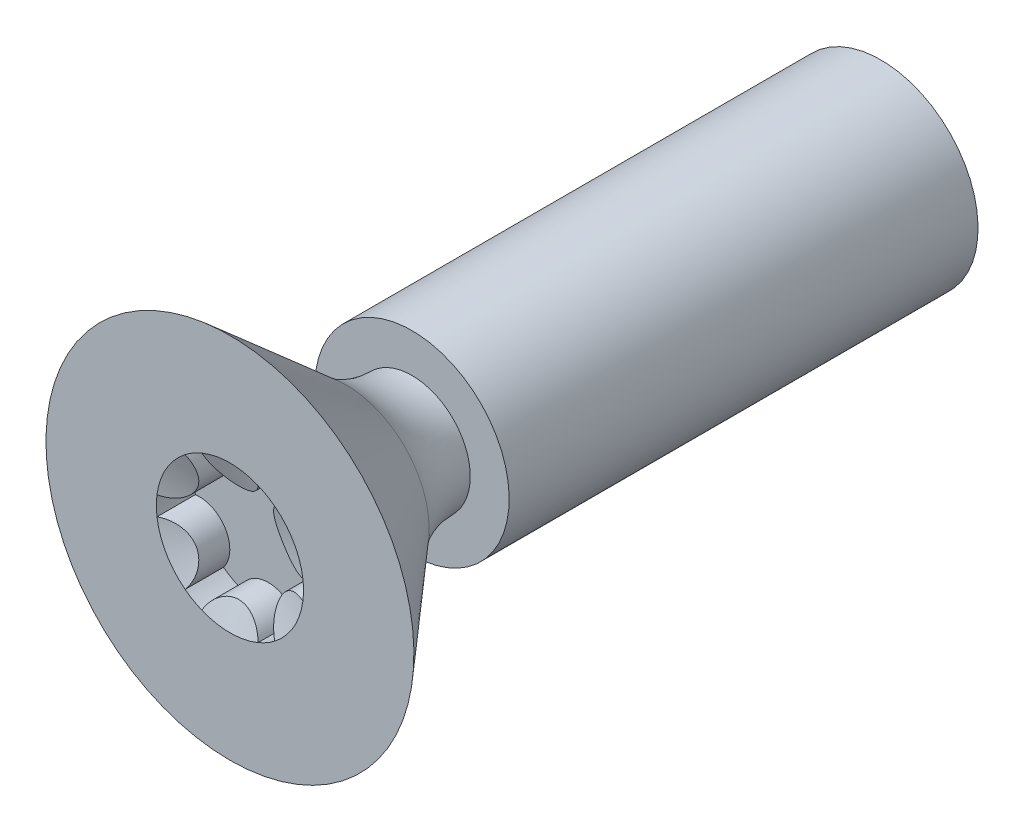
SolidWorks part; units mm, degrees
material "Plain Carbon Steel"
ref_plane "Front Plane" through (0, 0, 0) normal (0, 0, 1) x (1, 0, 0)
ref_plane "Top Plane" through (0, 0, 0) normal (0, 1, 0) x (1, 0, 0)
ref_plane "Right Plane" through (0, 0, 0) normal (1, 0, 0) x (0, 0, -1)
sketch "Sketch1" plane through (0, 0, 0) normal (1, 0, 0) x (0, 0, -1)
  line L0 (-4.7625, 0) -> (4.7625, 0) construction
  line L1 (4.7625, 0) -> (4.7625, 1.4224) construction
  line L2 (4.7625, 1.4224) -> (-3.0607, 1.4224) construction
  line L4 (-4.7625, 2.6924) -> (-4.7625, 0) construction
  line L5 (4.7625, -1.4224) -> (4.7625, 1.4224) construction
  line L6 (4.6831, 1.5599) -> (5.3181, 0.46) construction
  line L7 (5.3181, 0.46) -> (5.9531, 1.5599) construction
  line L8 (5.9531, 1.5599) -> (4.6831, 1.5599) construction
  line L9 (5.3181, 0.46) -> (5.3181, 0.5975) construction
  line L10 (5.3181, 1.5599) -> (5.3181, 1.4224) construction
  line L11 (5.8738, 1.4224) -> (4.7625, 1.4224) construction
  line L12 (5.3181, 1.4911) -> (5.9134, 1.4911) construction
  line L13 (5.3181, 1.4911) -> (4.7228, 1.4911) construction
  line L14 (5.2388, 0.5975) -> (5.3975, 0.5975) construction
  line L15 (-4.7625, 2.6924) -> (-3.0607, 0.7347) construction
  line L16 (2.8575, 1.4224) -> (2.8575, 0) construction
  line L17 (2.8575, 1.4224) -> (3.4925, 1.3104) construction
  line L18 (3.4925, 1.3104) -> (4.1275, 1.1985) construction
  line L19 (4.1275, 1.1985) -> (4.7625, 1.0865) construction
  line L20 (-4.7625, 0.7347) -> (-3.0607, 0.7347) construction
  line L21 (-3.0607, 1.4224) -> (-3.0607, 0.7347) construction
  line L22 (-3.1639, 0.8534) -> (2.8575, 0.8534) construction
  line L23 (-4.7625, 2.6924) -> (-2.647, 0.8534) construction
  line L24 (5.091, 0.8534) -> (5.5453, 0.8534) construction
  line L25 (-2.4257, 1.4224) -> (-2.9947, 0.8534) construction
  line L26 (-4.7625, 2.1336) -> (-2.3749, 0) construction
  line L27 (-4.7625, 0.3683) -> (-2.787, 0.3683) construction
  line L28 (-2.647, 0.8534) -> (-1.6652, 0) construction
  line L30 (-2.0989, 0) -> (-2.0989, 1.4224) construction
  line L31 (-1.1464, 0) -> (-1.1464, 1.4224) construction
  arc A1 (-3.2316, 0.9313) -> (-3.0607, 0.8534) centre (-3.0607, 1.0799) ccw construction
  arc A2 (-3.0607, 1.213) -> (-2.0989, 0.8534) centre (-2.0989, 2.3195) ccw construction
  point P0 (0.9525, 1.4224)
  point P4 (0, 0)
  point P10 (4.7625, 0)
  point P41 (-2.833, 1.0151)
  point P45 (-4.7625, 1.077)
  point P55 (-4.252, 0.7347)
  dimension "Length" = 9.525
  dimension "Screw OD" = 2.8448
  dimension "Head DIa" = 5.3848
  dimension "Pitch" = 1.27
  dimension "D2" = 0.1588
  dimension "D3" = 41
  dimension "D4" = 10
  dimension "D5" = 1.27
  dimension "Head Ht" = 1.7018
  dimension "D6" = 0.569
  dimension "D1" = 3.81
  dimension "D7" = 49
  dimension "D8" = 45
  dimension "D9" = 0.635
  dimension "D10" = 2.1539
  dimension "Recess Wd" = 0.7366
  dimension "Recess Dia" = 4.2672
  dimension "Recess Dp" = 2.3876
  dimension "D11" = 0.9525
  dimension "D12" = 0.5105
sketch "Sketch2" plane through (0, 0, 0) normal (0, 0, 1) x (1, 0, 0)
  line L0 (0, 0) -> (1.2318, -0.7112) construction
  line L1 (0, 0) -> (-1.2318, -0.7112) construction
  line L2 (0, 0.46) -> (0, 1.5599) construction
  line L5 (0, 2.6924) -> (0, 0) construction
  line L12 (0, 0) -> (0.5385, 0.9327) construction
  line L13 (0, 0) -> (-0.5385, 0.9327) construction
  line L14 (0, 0) -> (-0.4121, 0.995) construction
  line L15 (0, 0) -> (0.4121, 0.995) construction
  line L17 (0, -1.4224) -> (0, 1.4224) construction
  circle A7 centre (0, 0) radius 1.4224 construction
  circle A9 centre (0, 0) radius 1.077 construction
  arc A10 (-0.4121, 0.995) -> (0.4121, 0.995) centre (0, 1.1657) ccw construction
  arc A11 (-0.2886, 1.3437) -> (0.2886, 1.3437) centre (0, 0.8534) cw construction
  arc A12 (-1.308, -0.4219) -> (-1.0194, -0.9218) centre (-0.7391, -0.4267) ccw construction
  arc A13 (1.308, -0.4219) -> (1.0194, -0.9218) centre (0.7391, -0.4267) cw construction
  arc A14 (-1.308, -0.4219) -> (-0.2886, 1.3437) centre (0.7611, -0.4394) cw construction
  arc A15 (0.2886, 1.3437) -> (1.308, -0.4219) centre (-0.7611, -0.4394) cw construction
  arc A16 (1.0194, -0.9218) -> (-1.0194, -0.9218) centre (0, 0.8788) cw construction
  circle A17 centre (0, 0) radius 0.8534 construction
  point P0 (0, 2.6924)
  point P17 (1.2318, -0.7112)
  point P19 (-1.2318, -0.7112)
  point P21 (0, 0.8534)
  point P22 (1.2318, -0.7112)
  point P25 (0, -1.1904)
  point P26 (-1.2318, -0.7112)
  point P29 (0, 1.4224)
  point P66 (-0.7391, -0.4267)
  dimension "D1" = 0.569
  dimension "D2" = 120
  dimension "D3" = 120
  dimension "D6" = 7.5
  dimension "D7" = 7.5
  dimension "D8" = 30
  dimension "D9" = 30
  dimension "D4" = 0.0254
sketch "Sketch3" plane through (0, 0, 0) normal (1, 0, 0) x (0, 0, -1)
  line L0 (4.7625, 0) -> (4.7625, 1.4224) construction
  line L1 (-4.7625, 0) -> (4.7625, 0) construction
  line L2 (4.7625, 1.4224) -> (-3.0607, 1.4224) construction
  line L3 (-2.0989, 1.4224) -> (-2.0989, 0.8534)
  line L4 (-4.7625, 2.6924) -> (-4.7625, 0) construction
  line L5 (4.7625, 0) -> (4.7625, 1.4224)
  line L6 (-4.7625, 0) -> (4.7625, 0)
  line L7 (4.7625, 1.4224) -> (-2.0989, 1.4224)
  line L9 (-4.7625, 2.6924) -> (-4.7625, 0)
  line L15 (-4.7625, 2.6924) -> (-2.647, 0.8534) construction
  line L17 (-4.7625, 2.6924) -> (-3.0607, 1.213)
  arc A0 (-3.0607, 1.213) -> (-2.0989, 0.8534) centre (-2.0989, 2.3195) ccw construction
  arc A1 (-3.0607, 1.213) -> (-2.0989, 0.8534) centre (-2.0989, 2.3195) ccw
revolve "Revolve1" add sketch "Sketch3" angle 360 about L0
ref_plane "Plane1" through (0, 0, 4.7625) normal (0, 0, 1) x (1, 0, 0)
ref_plane "Plane5" through (0, 0, -2.8575) normal (0, 0, 1) x (1, 0, 0)
ref_plane "Plane6" through (0, 0, 2.0989) normal (0, 0, 1) x (1, 0, 0)
ref_plane "Plane7" through (0, 0, 1.1464) normal (0, 0, 1) x (1, 0, 0)
sketch "Sketch21" plane through (0, 0, 4.7625) normal (0, 0, 1) x (1, 0, 0)
  line L0 (0, 0) -> (-0.5385, 0.9327) construction
  line L3 (0, 0) -> (0.5385, 0.9327) construction
  line L4 (0, 0) -> (-0.5385, 0.9327)
  line L7 (0, 0) -> (0.5385, 0.9327)
  circle A0 centre (0, 0) radius 1.077 construction
  arc A1 (-0.4121, 0.995) -> (0.4121, 0.995) centre (0, 1.1657) ccw construction
  arc A2 (0.5385, 0.9327) -> (0.4121, 0.995) centre (0, 0) ccw
  arc A3 (-0.4121, 0.995) -> (0.4121, 0.995) centre (0, 1.1657) ccw
  arc A4 (-0.4121, 0.995) -> (-0.5385, 0.9327) centre (0, 0) ccw
extrude "Cut-Extrude14" cut sketch "Sketch21" against normal blind 0.5616
pattern_circular "CirPattern1" count 6 over 360 about axis through (0, 0, 4.7625) along (0, 0, -1) of "Cut-Extrude14"
sketch "Sketch22" plane through (0, 0, 4.7625) normal (0, 0, 1) x (1, 0, 0)
  circle A0 centre (0, 0) radius 1.077 construction
  circle A1 centre (0, 0) radius 1.077
extrude "Cut-Extrude15" cut sketch "Sketch22" against normal up to vertex (0.5105 mm away) draft 70 up to point (0, 0.7347, 4.252)
sketch "Sketch20" plane through (0, 0, 0) normal (1, 0, 0) x (0, 0, -1)
  line L0 (4.7625, -1.4224) -> (4.7625, 1.4224) construction
  point P0 (2.8575, -1.1904)
  dimension "D1" = 1.905
sketch "Sketch24" plane through (0, 0, 4.7625) normal (0, 0, 1) x (1, 0, 0)
  circle A0 centre (0, 0) radius 2.6924
  point P0 (0.6556, -0.8544)
ref_axis "Center Axis 1" through (0, 0, 4.7625) along (0, 0, -1)
ref_plane "Contact Plane 1" through (0, 0, -4.7625) normal (0, 0, -1) x (-1, 0, 0)
ref_plane "Contact Plane 2" through (0, 0, 3.0607) normal (0, 0, 1) x (1, 0, 0)
sketch "Sketch8" [suppressed] plane through (0, 0, -4.7625) normal (0, 0, -1) x (-1, 0, 0)
  line L0 (0, -1.4224) -> (0, 1.4224) construction
  circle A0 centre (0, 0) radius 1.4224
  point P0 (0, 1.4224)
curve "Helix/Spiral1" [suppressed] pitch 1.27 height 9.0932 turns 7.16
split "Split1" [suppressed] bodies to split 147
sketch "Sketch9" [suppressed] plane through (0, 0, 0) normal (1, 0, 0) x (0, 0, -1)
  line L0 (4.7228, 1.4911) -> (5.091, 0.8534)
  line L2 (5.5453, 0.8534) -> (5.9134, 1.4911)
  line L3 (4.7228, 1.4911) -> (5.9134, 1.4911)
  line L5 (5.091, 0.8534) -> (5.5453, 0.8534)
sweep "Cut-Sweep1" [suppressed] cut profiles "Sketch9" path "Helix/Spiral1"
sketch "Sketch11" [suppressed] plane through (0, 0, 2.0989) normal (0, 0, 1) x (1, 0, 0)
  arc A0 (1.0194, -0.9218) -> (1.308, -0.4219) centre (0.7391, -0.4267) ccw construction
  arc A1 (-1.0194, -0.9218) -> (1.0194, -0.9218) centre (0, 0.8788) ccw construction
  arc A2 (-1.308, -0.4219) -> (-1.0194, -0.9218) centre (-0.7391, -0.4267) ccw construction
  arc A3 (-0.2886, 1.3437) -> (-1.308, -0.4219) centre (0.7611, -0.4394) ccw construction
  arc A4 (0.2886, 1.3437) -> (-0.2886, 1.3437) centre (0, 0.8534) ccw construction
  arc A5 (1.308, -0.4219) -> (0.2886, 1.3437) centre (-0.7611, -0.4394) ccw construction
  arc A6 (1.0194, -0.9218) -> (1.308, -0.4219) centre (0.7391, -0.4267) ccw
  arc A7 (-1.0194, -0.9218) -> (1.0194, -0.9218) centre (0, 0.8788) ccw
  arc A8 (-1.308, -0.4219) -> (-1.0194, -0.9218) centre (-0.7391, -0.4267) ccw
  arc A9 (-0.2886, 1.3437) -> (-1.308, -0.4219) centre (0.7611, -0.4394) ccw
  arc A10 (0.2886, 1.3437) -> (-0.2886, 1.3437) centre (0, 0.8534) ccw
  arc A11 (1.308, -0.4219) -> (0.2886, 1.3437) centre (-0.7611, -0.4394) ccw
extrude "Cut-Extrude3" [suppressed] cut sketch "Sketch11" against normal through all flip side to cut
sketch "Sketch18" [suppressed] plane through (0, 0, 1.1464) normal (0, 0, 1) x (1, 0, 0)
  circle A0 centre (0, 0) radius 1.4224
  point P0 (0, 1.4224)
extrude "Cut-Extrude13" [suppressed] cut sketch "Sketch18" along normal through all draft 35.5 flip side to cut draft outward yes
sketch "Sketch12" [suppressed] plane through (0, 0, -2.8575) normal (0, 0, 1) x (1, 0, 0)
  arc A0 (-1.308, -0.4219) -> (-1.0194, -0.9218) centre (-0.7391, -0.4267) ccw construction
  arc A1 (-1.0194, -0.9218) -> (1.0194, -0.9218) centre (0, 0.8788) ccw construction
  arc A2 (1.0194, -0.9218) -> (1.308, -0.4219) centre (0.7391, -0.4267) ccw construction
  arc A3 (1.308, -0.4219) -> (0.2886, 1.3437) centre (-0.7611, -0.4394) ccw construction
  arc A4 (0.2886, 1.3437) -> (-0.2886, 1.3437) centre (0, 0.8534) ccw construction
  arc A5 (-0.2886, 1.3437) -> (-1.308, -0.4219) centre (0.7611, -0.4394) ccw construction
  arc A6 (-1.308, -0.4219) -> (-1.0194, -0.9218) centre (-0.7391, -0.4267) ccw
  arc A7 (-1.0194, -0.9218) -> (1.0194, -0.9218) centre (0, 0.8788) ccw
  arc A8 (1.0194, -0.9218) -> (1.308, -0.4219) centre (0.7391, -0.4267) ccw
  arc A9 (1.308, -0.4219) -> (0.2886, 1.3437) centre (-0.7611, -0.4394) ccw
  arc A10 (0.2886, 1.3437) -> (-0.2886, 1.3437) centre (0, 0.8534) ccw
  arc A11 (-0.2886, 1.3437) -> (-1.308, -0.4219) centre (0.7611, -0.4394) ccw
extrude "Cut-Extrude4" [suppressed] cut sketch "Sketch12" against normal through all draft 7 flip side to cut draft outward yes
sketch "Sketch15" [suppressed] plane through (0, 0, 0) normal (1, 0, 0) x (0, 0, -1)
  line L14 (-1.2316, 0) -> (-2.0989, 0)
  line L17 (-2.0989, 0) -> (-2.0989, 0.8534)
  line L18 (-2.0989, 0.8534) -> (-1.2316, 0.8534)
  line L19 (-3.1639, 0.8534) -> (2.8575, 0.8534) construction
  line L20 (-1.2316, 0.8534) -> (-1.2316, 0)
  point P3 (-1.6652, 0)
revolve "Revolve3" [suppressed] add sketch "Sketch15" angle 360 about L0
equation "\"D2@Sketch1\"=\"Pitch@Sketch1\"/8"
equation "\"D5@Sketch1\"=\"Pitch@Sketch1\""
equation "\"D6@Sketch1\"=\"Screw OD@Sketch1\"*.2"
equation "\"D9@Sketch1\"=\"Pitch@Sketch1\"*.5"
equation "\"D1@Sketch1\"=\"Pitch@Sketch1\"*3"
equation "\"D1@Sketch2\"=\"Screw OD@Sketch1\"*.2"
equation "\"D4@Helix/Spiral1\"=\"Pitch@Sketch1\""
equation "\"D3@Helix/Spiral1\"=\"Length@Sketch1\"-\"Head Ht@Sketch1\"+\"Pitch@Sketch1\""
equation "\"D10@Sketch1\"=\"Head DIa@Sketch1\"*.4"
equation "\"D11@Sketch1\"=\"Pitch@Sketch1\"*.75"
equation "\"D1@Sketch20\"=\"Pitch@Sketch1\"*1.5"
equation "\"D1@Cut-Extrude14\"=\"Head Ht@Sketch1\"*.33"
equation "\"D12@Sketch1\"=\"Head Ht@Sketch1\"*.3"
